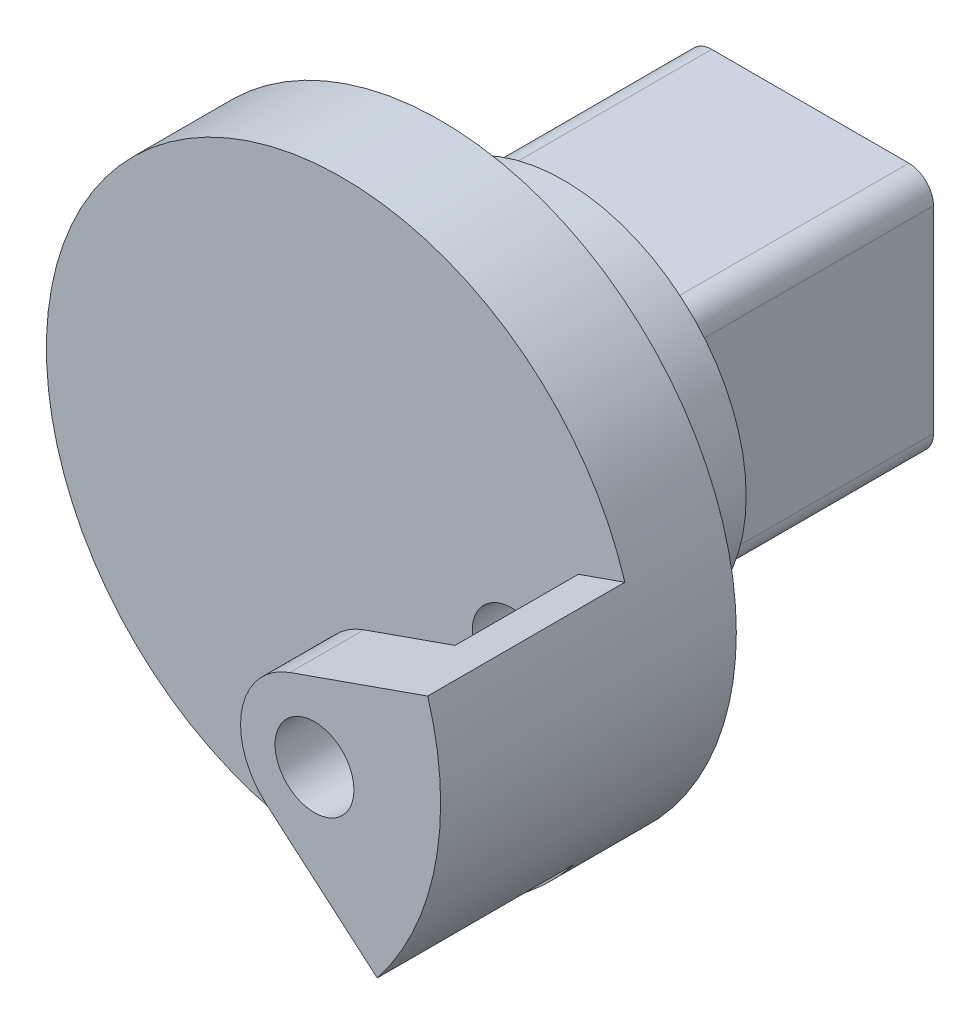
SolidWorks part; units mm, degrees
ref_plane "Front Plane" through (0, 0, 0) normal (0, 0, 1) x (1, 0, 0)
ref_plane "Top Plane" through (0, 0, 0) normal (0, 1, 0) x (1, 0, 0)
ref_plane "Right Plane" through (0, 0, 0) normal (1, 0, 0) x (0, 0, -1)
sketch "Sketch1" plane through (0, 0, 0) normal (0, 0, 1) x (1, 0, 0)
  line L1 (-5, -5) -> (5, -5)
  line L2 (-5, -5) -> (-5, 5)
  line L3 (-5, 5) -> (5, 5)
  line L4 (5, -5) -> (5, 5)
  line L5 (-5, -5) -> (5, 5) construction
  line L6 (-5, 5) -> (5, -5) construction
  circle A0 centre (0, 0) radius 7.4
  dimension "D1" = 14.8
  dimension "D3" = 10
  dimension "D4" = 10
extrude "Boss-Extrude1" add sketch "Sketch1" against normal blind 10 contours L4 L3 L2 L1
extrude "Boss-Extrude2" add sketch "Sketch1<4>" along normal blind 5 contours A0
sketch "Sketch1<4>" plane through (0, 0, 0) normal (0, 0, 1) x (1, 0, 0) same geometry as "Sketch1"
fillet "Fillet1" radius 1 4 edges at (5, 5, -5) (-5, 5, -5) (-5, -5, -5) (5, -5, -5)
sketch "Sketch2" plane through (0, 0, 0) normal (0, 0, 1) x (1, 0, 0)
  circle A0 centre (0, 0) radius 12
  dimension "D1" = 24
extrude "Boss-Extrude3" add sketch "Sketch2" along normal blind 4 from surface starting at face at (7.4, 0, 5)
sketch "Sketch3" plane through (0, 0, 0) normal (0, 0, 1) x (1, 0, 0)
  line L0 (0, 0) -> (0, 16.1137) construction
  line L1 (0, 0) -> (0, -19.6849) construction
  line L2 (0, 0) -> (-9.7508, 13.9256) construction
  line L3 (0, 0) -> (-15.2488, -18.1728) construction
  line L4 (0, 0) -> (-26.1304, 0) construction
  line L5 (-3.1547, 4.5053) -> (5.5819, 10.6227)
  line L6 (-3.5353, -4.2132) -> (4.6348, -11.0688)
  circle A0 centre (0, 0) radius 8.5 construction
  circle A1 centre (-4.8754, 6.9628) radius 3
  circle A2 centre (-5.4637, -6.5114) radius 3
  circle A3 centre (-8.5, 0) radius 1.5
  circle A4 centre (0, 0) radius 5.5
  circle A6 centre (0, 0) radius 12
  dimension "D3" = 6
  dimension "D4" = 6
  dimension "D5" = 17
  dimension "D6" = 3
  dimension "D7" = 24
  dimension "D1" = 55
  dimension "D2" = 50
sketch "Sketch4" plane through (0, 0, 0) normal (0, 0, 1) x (1, 0, 0)
  line L0 (0, 0) -> (-31.5, 0) construction
  line L1 (-31.5, 0) -> (-31.5, 5.9) construction
  line L2 (-31.5, 5.9) -> (0, 0) construction
  line L3 (0, 0) -> (6.8804, -1.2887) construction
  line L4 (5.8843, 1.5411) -> (11.4755, 3.5091)
  line L5 (4.9277, -3.5662) -> (9.4276, -7.4243)
  circle A0 centre (0, 0) radius 7 construction
  circle A3 centre (6.8804, -1.2887) radius 3
  arc A4 (9.4276, -7.4243) -> (11.4755, 3.5091) centre (0, 0) ccw
  circle A5 centre (0, 0) radius 12 construction
  circle A6 centre (6.8804, -1.2887) radius 1.6
  arc A7 (7.9077, -6.1212) -> (9.5869, 2.8444) centre (0, 0) ccw
  dimension "D3" = 6
  dimension "D4" = 14
  dimension "D7" = 3.2
  dimension "D1" = 31.5
  dimension "D2" = 5.9
  dimension "D5" = 150
  dimension "D6" = 150
extrude "Boss-Extrude4" add sketch "Sketch4" along normal blind 5 from surface contours A7 L5 A4 L4 region at (10.4359, -1.9547, 0) starting at face at (12, 0, 9)
extrude "Boss-Extrude5" add sketch "Sketch4<5>" along normal blind 3 from surface contours A7 L5 A4 L4 | A3 A7 L4 | L5 A7 A3 | A3 A6 region at (8.957, 1.4793, 0) region at (8.5651, 1.0903, 0) region at (10.4359, -1.9547, 0) region at (7.8145, -4.6207, 0) starting at face at (10.2057, -1.9115, 14)
sketch "Sketch4<5>" plane through (0, 0, 0) normal (0, 0, 1) x (1, 0, 0) same geometry as "Sketch4"
extrude "Cut-Extrude1" cut sketch "Sketch4<7>" against normal blind 3.5 from surface contours A6 starting at face at (4.3083, -0.8069, 9)
sketch "Sketch4<7>" plane through (0, 0, 0) normal (0, 0, 1) x (1, 0, 0) same geometry as "Sketch4"
